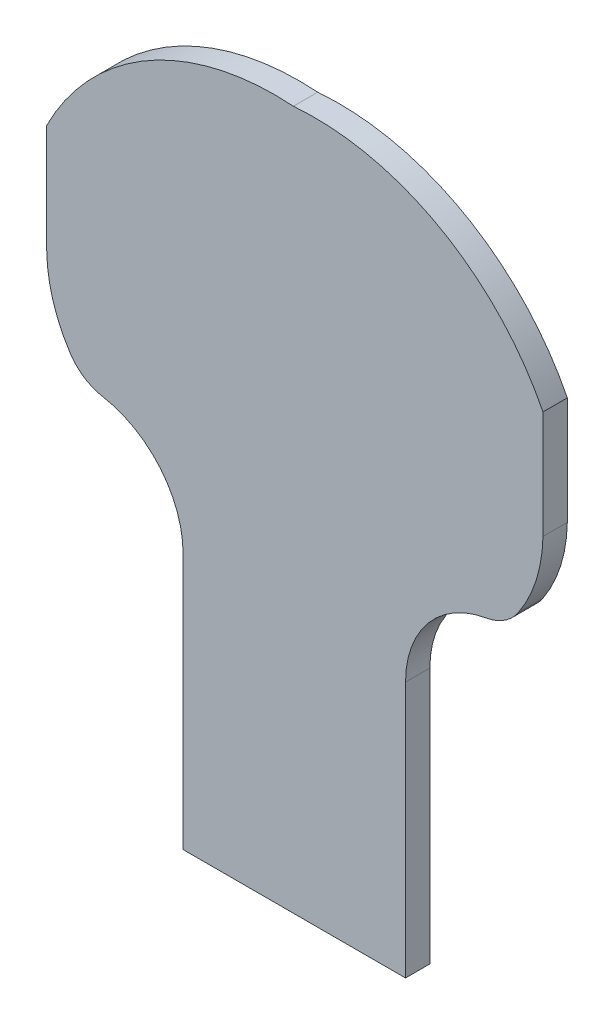
SolidWorks part; units mm, degrees
ref_plane "Спереди" through (0, 0, 0) normal (0, 0, 1) x (1, 0, 0)
ref_plane "Сверху" through (0, 0, 0) normal (0, 1, 0) x (1, 0, 0)
ref_plane "Справа" through (0, 0, 0) normal (1, 0, 0) x (0, 0, -1)
sketch "Эскиз1" plane through (0, 0, 0) normal (0, 0, 1) x (1, 0, 0)
  line L0 (29.1233, 63.4796) -> (68.8158, 63.4796) construction
  line L1 (51.0512, 63.4796) -> (51.0512, 85.6506)
  line L2 (-50.9488, 85.6506) -> (-50.9488, 63.4796)
  line L3 (-22.9109, -29.2324) -> (22.8017, -29.2324)
  line L4 (-0.2532, -199845.2635) -> (-0.2532, 200185.0944) construction
  line L7 (-22.9109, 23.4364) -> (-22.9109, -29.2324)
  line L9 (22.8017, 23.4364) -> (22.8017, -29.2324)
  arc A0 (-22.9109, 23.4364) -> (-39.466, 43.1375) centre (-42.9109, 23.4364) ccw
  arc A1 (39.4018, 43.1453) -> (22.8017, 23.4364) centre (42.8017, 23.4364) ccw
  arc A2 (-39.466, 43.1375) -> (-46.1137, 47.5161) centre (-37.7436, 52.9881) cw
  arc A3 (-50.9488, 63.4796) -> (-46.1137, 47.5161) centre (-21.2781, 63.7525) ccw
  arc A4 (51.0512, 63.4796) -> (46.0058, 47.428) centre (21.279, 64.0191) cw
  arc A5 (46.0058, 47.428) -> (39.4018, 43.1453) centre (37.7018, 52.9998) cw
  arc A6 (-50.9488, 85.6506) -> (-0.2532, 114.4085) centre (-4.0434, 62.027) cw
  arc A7 (51.0512, 85.6506) -> (-0.2532, 114.4085) centre (4.1229, 62.0727) ccw
  point P0 (0, 0)
  point P14 (-23.267, 44.4248)
  point P17 (23.1578, 44.4248)
  point P20 (-50.9488, 44.4248)
  point P23 (51.0512, 44.4248)
  dimension "D1" = 20
  dimension "D2" = 10
extrude "Вытянуть1" add sketch "Эскиз1" along normal blind 5
sketch "Эскиз2" plane through (0, 0, 0) normal (0, 0, 1) x (1, 0, 0)
  line L0 (0, 27.6566) -> (0, -11.0597) construction
